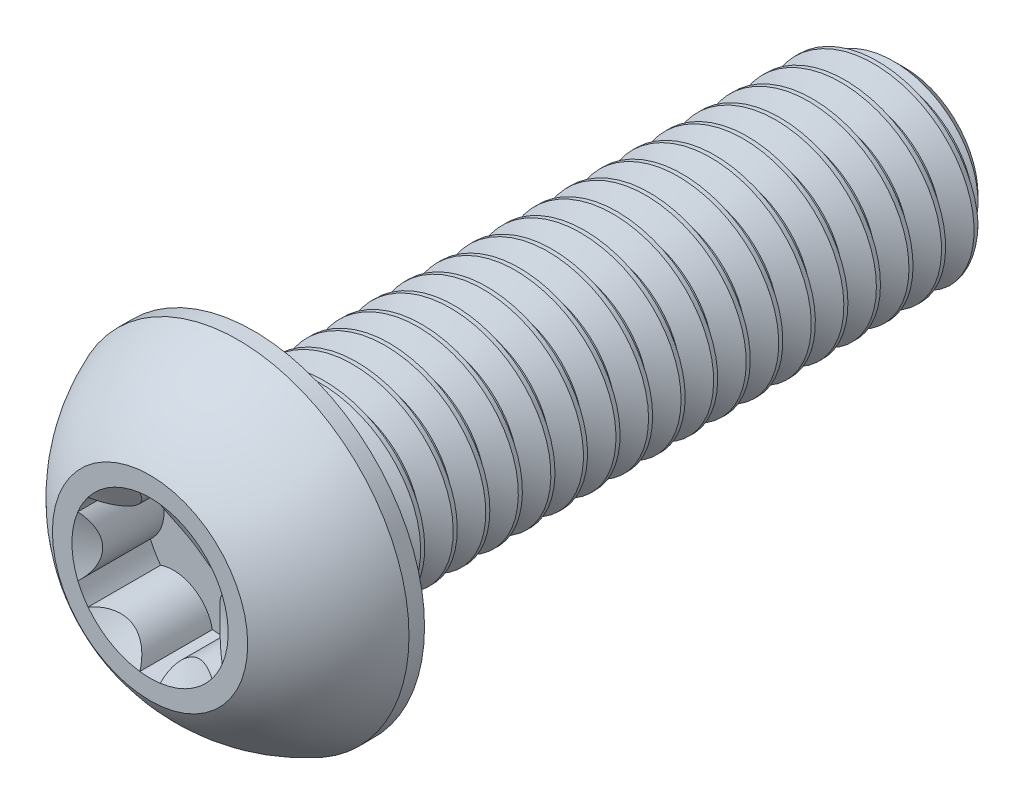
SolidWorks part; units mm, degrees
material "Plain Carbon Steel"
ref_plane "Front" through (0, 0, 0) normal (0, 0, 1) x (1, 0, 0)
ref_plane "Top" through (0, 0, 0) normal (0, 1, 0) x (1, 0, 0)
ref_plane "Right" through (0, 0, 0) normal (1, 0, 0) x (0, 0, -1)
sketch "Sketch1" plane through (0, 0, 0) normal (1, 0, 0) x (0, 0, -1)
  line L2 (5.0546, 4.7625) -> (36.8046, 4.7625)
  line L3 (36.8046, 4.7625) -> (36.8046, 0)
  line L4 (36.8046, 0) -> (5.0546, 0)
  line L6 (4.2964, 8.3312) -> (5.0546, 8.3312) construction
  line L7 (36.8046, 4.7625) -> (36.8046, -4.7625) construction
  line L8 (0, 0) -> (5.0546, 0) construction
  line L9 (5.0546, 8.3312) -> (5.0546, -8.3312) construction
  line L11 (5.0546, 4.7625) -> (5.0546, 0)
  line L14 (0, 0) -> (0, 4.7625) construction
  arc A3 (0, 4.7625) -> (4.2964, 8.3312) centre (7.5862, 0) cw construction
  dimension "D1" = 0.7582
  dimension "Head Ht" = 5.0546
  dimension "Head Dia" = 16.6624
  dimension "Dia" = 9.525
  dimension "Lg" = 31.75
revolve "Revolve1" add sketch "Sketch1" angle 360 mid plane about L4
sketch "Sketch3" plane through (0, 0, -36.8046) normal (0, 0, -1) x (-1, 0, 0)
  circle A0 centre (0, 0) radius 4.7625
curve "Helix/Spiral1" pitch 1.5875 height 33.3375 turns 21
sketch "Sketch2" plane through (0, 0, 0) normal (1, 0, 0) x (0, 0, -1)
  line L0 (36.8046, 4.7625) -> (38.1937, 4.7625)
  line L1 (38.1937, 4.7625) -> (37.5984, 3.7314)
  line L2 (37.5984, 3.7314) -> (37.3999, 3.7314)
  line L3 (37.3999, 3.7314) -> (36.8046, 4.7625)
  line L4 (37.1023, 4.2469) -> (37.896, 4.2469) construction
  dimension "D1" = 60
  dimension "D2" = 0.1984
  dimension "D3" = 0.7937
chamfer "Chamfer1" distance 1.1906 angle 45 1 edges at (0, 4.7625, -36.8046)
sweep "Cut-Sweep1" cut profiles "Sketch2" path "Helix/Spiral1"
sketch "Sketch7" plane through (0, 0, 0) normal (1, 0, 0) x (0, 0, -1)
  line L0 (0, 0) -> (0, 4.7625) construction
  line L6 (4.2964, 8.3312) -> (5.0546, 8.3312) construction
  line L8 (0, 0) -> (5.0546, 0) construction
  line L11 (5.0546, 8.3312) -> (5.0546, -8.3312) construction
  line L12 (4.2964, 8.3312) -> (5.0546, 8.3312)
  line L13 (0, 0) -> (5.0546, 0)
  line L15 (5.0546, 8.3312) -> (5.0546, 0)
  line L16 (0, 4.7625) -> (0, 0)
  arc A2 (4.2964, 8.3312) -> (0, 4.7625) centre (7.5862, 0) ccw construction
  arc A3 (4.2964, 8.3312) -> (0, 4.7625) centre (7.5862, 0) ccw
revolve "Revolve2" add sketch "Sketch7" angle 360 mid plane about L13
sketch "Sketch5" plane through (0, 0, 0) normal (0, 0, 1) x (1, 0, 0)
  line L1 (0, 0) -> (-3.81, 0) construction
  line L2 (0, 0) -> (-3.2996, 1.905) construction
  line L3 (0, 0) -> (-3.2996, -1.905) construction
  line L4 (-3.2996, -1.905) -> (0, 0)
  line L5 (0, 0) -> (-3.2996, 1.905)
  line L6 (0, 0) -> (-3.52, -1.458) construction
  line L7 (0, 3.81) -> (0, 3.3338) construction
  line L8 (0, 3.3338) -> (0, 2.8575) construction
  circle A0 centre (0, 0) radius 3.81 construction
  circle A3 centre (0, 0) radius 3.3338 construction
  circle A4 centre (0, 0) radius 2.8575 construction
  arc A5 (-3.52, -1.458) -> (-3.52, 1.458) centre (-4.7932, 0) ccw
  arc A6 (-3.52, 1.458) -> (-3.2996, 1.905) centre (0, 0) cw
  arc A7 (-3.52, -1.458) -> (-3.2996, -1.905) centre (0, 0) ccw
  dimension "D3" = 7.5
  dimension "D4" = 7.62
  dimension "D5" = 5.715
  dimension "D1" = 30
extrude "Cut-Extrude2" cut sketch "Sketch5" against normal blind 3.5382
pattern_circular "CirPattern1" count 6 over 360 about axis through (0, 0, 0) along (0, 0, 1) of "Cut-Extrude2"
sketch "Sketch11" plane through (0, 0, 0) normal (0, 0, 1) x (1, 0, 0)
  circle A1 centre (0, 0) radius 3.81 construction
  circle A2 centre (0, 0) radius 3.81
extrude "Cut-Extrude3" cut sketch "Sketch11" against normal blind 3.5382 draft 60
sketch "Sketch9" [suppressed] plane through (0, 0, -5.0292) normal (0, 0, 1) x (1, 0, 0)
  circle A2 centre (0, 0) radius 4.7625
extrude "Boss-Extrude2" [suppressed] add sketch "Sketch9" against normal offset from surface (6.35 mm away) 31.75
sketch "Sketch10" plane through (0, 0, 0) normal (1, 0, 0) x (0, 0, -1)
  line L0 (36.8046, 4.7625) -> (36.8046, -4.7625) construction
  point P0 (34.4233, -4.7625)
  dimension "D1" = 2.3813
equation "\"D3@Helix/Spiral1\" = \"Lg@Sketch1\" + \"D4@Helix/Spiral1\""
equation "\"D2@Sketch2\" = \"D4@Helix/Spiral1\" * .125"
equation "\"D3@Sketch2\" = \"D4@Helix/Spiral1\" * .5"
equation "\"D1@Chamfer1\" = \"D4@Helix/Spiral1\" * .75"
equation "\"D1@Cut-Extrude2\" = \"Head Ht@Sketch1\" * .7"
equation "\"D1@Sketch1\" = \"Head Ht@Sketch1\" * .15"
equation "\"D1@Sketch10\" = \"D4@Helix/Spiral1\" * 1.5"
equation "\"D1@Cut-Extrude3\" = \"D1@Cut-Extrude2\""
equation "\"D4@Sketch5\" = \"Dia@Sketch1\" * .8"
equation "\"D5@Sketch5\" = \"D4@Sketch5\" * .75"
